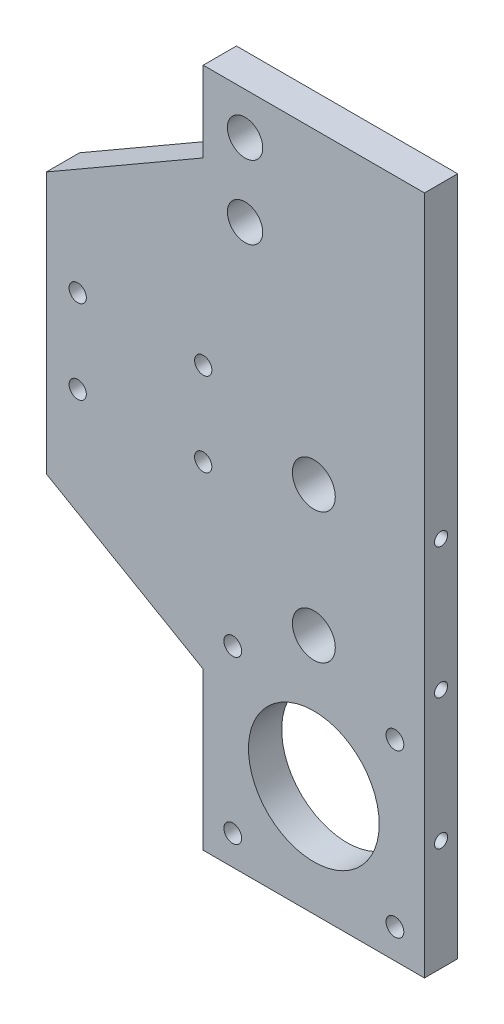
SolidWorks part; units mm, degrees
material "6061 Alloy"
ref_plane "Front Plane" through (0, 0, 0) normal (0, 0, 1) x (1, 0, 0)
ref_plane "Top Plane" through (0, 0, 0) normal (0, 1, 0) x (1, 0, 0)
ref_plane "Right Plane" through (0, 0, 0) normal (1, 0, 0) x (0, 0, -1)
sketch "Sketch2" plane through (0, 0, 0) normal (0, 0, 1) x (1, 0, 0)
  line L0 (0, 0) -> (0, -21.15) construction
  line L1 (-21.15, -21.15) -> (21.15, -21.15)
  line L2 (-21.15, -21.15) -> (-21.15, 108.85)
  line L3 (-21.15, 108.85) -> (21.15, 108.85)
  line L4 (21.15, -21.15) -> (21.15, 108.85)
  circle A0 centre (0, 0) radius 12.5
  circle A1 centre (0, 25) radius 4.1
  circle A2 centre (0, 50) radius 4.1
  dimension "D1" = 25
  dimension "D5" = 25
  dimension "D7" = 8.2
  dimension "D2" = 21.15
  dimension "D3" = 42.3
  dimension "D4" = 130
  dimension "D6" = 25
extrude "Boss-Extrude1" add sketch "Sketch2" along normal blind 6.35
sketch "Sketch3" plane through (21.15, 0, 0) normal (-1, 0, 0) x (0, 0, 1)
  line L0 (6.35, -12.5) -> (6.35, 12.5) construction
  line L1 (6.35, 20.9) -> (6.35, 29.1) construction
  line L2 (6.35, 45.9) -> (6.35, 54.1) construction
  line L3 (6.35, -12.5) -> (6.35, 12.5) construction
  line L4 (6.35, 20.9) -> (6.35, 29.1) construction
  line L5 (6.35, 45.9) -> (6.35, 54.1) construction
  line L6 (3.175, 108.85) -> (3.175, -21.15) construction
  line L7 (6.35, 108.85) -> (0, 108.85) construction
  line L8 (6.35, -21.15) -> (0, -21.15) construction
  line L9 (6.35, 0) -> (3.175, 0) construction
  line L10 (6.35, 25) -> (3.175, 25) construction
  line L11 (6.35, 50) -> (3.175, 50) construction
  point P13 (3.175, 0)
  point P16 (3.175, 25)
  point P18 (3.175, 50)
hole_wizard "Tap Drill for M3x0.5 Tap1" positions "Sketch3" profile "Sketch4" hole size "M3x0.5" standard "ANSI Metric"
sketch "Sketch4" plane through (21.15, 50, 3.175) normal (0, 1, 0) x (0, 0, -1)
  line L0 (0, 0) -> (0, 21.9011)
  line L1 (0, 21.9011) -> (1.25, 21.15)
  line L2 (1.25, 21.15) -> (1.25, 0)
  line L5 (1.25, 0) -> (0, 0)
  line L10 (0, 21.9011) -> (-1.25, 21.15) construction
  line L11 (0, -6.35) -> (0, 107.95) construction
  dimension "Hole Dia." = 2.5
  dimension "Hole Depth" = 21.15
  dimension "Drill Angle" = 118
sketch "Sketch5" plane through (0, 0, 6.35) normal (0, 0, 1) x (1, 0, 0)
  line L1 (-15.5, -15.5) -> (15.5, -15.5) construction
  line L2 (-15.5, -15.5) -> (-15.5, 15.5) construction
  line L3 (-15.5, 15.5) -> (15.5, 15.5) construction
  line L4 (15.5, -15.5) -> (15.5, 15.5) construction
  line L5 (-15.5, -15.5) -> (15.5, 15.5) construction
  line L6 (-15.5, 15.5) -> (15.5, -15.5) construction
  point P0 (0, 0)
  dimension "D1" = 31
hole_wizard "M3 Clearance Hole1" positions "Sketch7" profile "Sketch9" hole size "M3" standard "ANSI Metric" end condition through all
sketch "Sketch7" plane through (0, 0, 6.35) normal (0, 0, 1) x (1, 0, 0)
  point P0 (-15.5, 15.5)
  point P3 (-15.5, -15.5)
  point P6 (15.5, -15.5)
  point P9 (15.5, 15.5)
sketch "Sketch9" plane through (-15.5, 15.5, 6.35) normal (1, 0, 0) x (0, -1, 0)
  line L0 (0, 0) -> (0, 6.35)
  line L1 (0, 6.35) -> (1.7, 6.35)
  line L2 (1.7, 6.35) -> (1.7, 0)
  line L5 (1.7, 0) -> (0, 0)
  line L11 (0, -6.35) -> (0, 107.95) construction
  dimension "Thru Hole Dia." = 3.4
  dimension "Thru Hole Depth" = 6.35
sketch "Sketch11" plane through (0, 0, 6.35) normal (0, 0, 1) x (1, 0, 0)
  line L0 (-13.15, 108.85) -> (-13.15, 78.85) construction
  line L1 (21.15, 108.85) -> (-21.15, 108.85) construction
  line L2 (-13.15, 78.85) -> (-21.15, 78.85) construction
  line L3 (-21.15, 108.85) -> (-21.15, -21.15) construction
  point P7 (-13.15, 100.85)
  point P8 (-13.15, 86.85)
  dimension "D1" = 8
  dimension "D2" = 8
  dimension "D3" = 30
  dimension "D4" = 8
hole_wizard "1/4 Clearance Hole1" positions "Sketch11" profile "Sketch12" hole size "1/4" standard "ANSI Inch" end condition through all
sketch "Sketch12" plane through (-13.15, 86.85, 6.35) normal (1, 0, 0) x (0, -1, 0)
  line L0 (0, 0) -> (0, 6.35)
  line L1 (0, 6.35) -> (3.3782, 6.35)
  line L2 (3.3782, 6.35) -> (3.3782, 0)
  line L5 (3.3782, 0) -> (0, 0)
  line L11 (0, -6.35) -> (0, 107.95) construction
  dimension "Thru Hole Dia." = 6.7564
  dimension "Thru Hole Depth" = 6.35
sketch "Sketch13" plane through (0, 0, 6.35) normal (0, 0, 1) x (1, 0, 0)
  line L0 (-21.15, 8.85) -> (-51.15, 26.1705)
  line L2 (-51.15, 26.1705) -> (-51.15, 76.1705)
  line L3 (-51.15, 76.1705) -> (-21.15, 93.491)
  line L4 (-21.15, 93.491) -> (-21.15, 8.85)
  line L6 (-21.15, 108.85) -> (-21.15, -21.15) construction
  dimension "D1" = 60
  dimension "D2" = 60
  dimension "D3" = 30
  dimension "D4" = 50
  dimension "D5" = 30
extrude "Boss-Extrude2" add sketch "Sketch13" against normal up to surface (6.35 mm away) up to face at (-9.7718, 100.85, 0)
sketch "Sketch14" plane through (0, 0, 6.35) normal (0, 0, 1) x (1, 0, 0)
  line L0 (-51.15, 51.1705) -> (-33.15, 51.1705) construction
  line L1 (-51.15, 76.1705) -> (-51.15, 26.1705) construction
  line L3 (-45.15, 43.1705) -> (-21.15, 43.1705) construction
  line L4 (-45.15, 43.1705) -> (-45.15, 59.1705) construction
  line L5 (-45.15, 59.1705) -> (-21.15, 59.1705) construction
  line L6 (-21.15, 43.1705) -> (-21.15, 59.1705) construction
  line L7 (-45.15, 43.1705) -> (-21.15, 59.1705) construction
  line L8 (-45.15, 59.1705) -> (-21.15, 43.1705) construction
  dimension "D1" = 16
  dimension "D2" = 24
  dimension "D3" = 18
hole_wizard "Tap Drill for M4x0.7 Tap1" positions "Sketch15" profile "Sketch16" hole size "M4x0.7" standard "ANSI Metric" end condition through all
sketch "Sketch15" plane through (0, 0, 6.35) normal (0, 0, 1) x (1, 0, 0)
  point P0 (-45.15, 59.1705)
  point P3 (-21.15, 59.1705)
  point P6 (-21.15, 43.1705)
  point P9 (-45.15, 43.1705)
sketch "Sketch16" plane through (-45.15, 59.1705, 6.35) normal (1, 0, 0) x (0, -1, 0)
  line L0 (0, 0) -> (0, 6.35)
  line L1 (0, 6.35) -> (1.65, 6.35)
  line L2 (1.65, 6.35) -> (1.65, 0)
  line L5 (1.65, 0) -> (0, 0)
  line L11 (0, -6.35) -> (0, 107.95) construction
  dimension "Thru Hole Dia." = 3.3
  dimension "Thru Hole Depth" = 6.35
